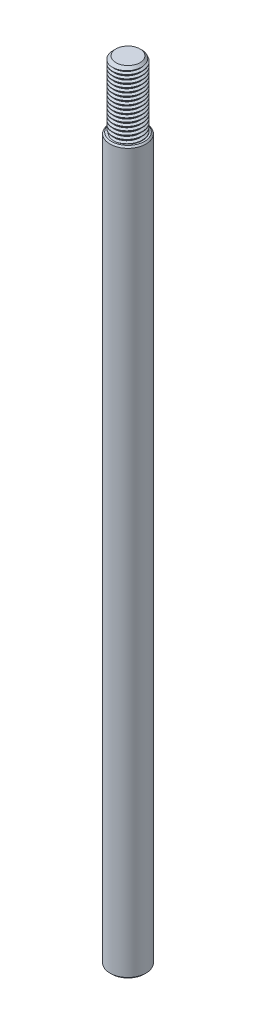
SolidWorks part; units mm, degrees
material "1.8507 (34CrAlMo5-10)"
ref_plane "Front Plane" through (0, 0, 0) normal (0, 0, 1) x (1, 0, 0)
ref_plane "Top Plane" through (0, 0, 0) normal (0, 1, 0) x (1, 0, 0)
ref_plane "Right Plane" through (0, 0, 0) normal (1, 0, 0) x (0, 0, -1)
sketch "Sketch1" plane through (0, 0, 0) normal (0, 1, 0) x (1, 0, 0)
  circle A0 centre (0, 0) radius 6
  dimension "D1" = 12
extrude "Boss-Extrude1" add sketch "Sketch1" along normal blind 262.5
sketch "Sketch4" plane through (0, 262.5, 0) normal (0, 1, 0) x (1, 0, 0)
  circle A0 centre (0, 0) radius 5
  dimension "D1" = 10
extrude "Cut-Extrude1" cut sketch "Sketch4" against normal blind 22 flip side to cut
chamfer "Chamfer2" distance 1 angle 45 1 edges at (0, 262.5, 5)
chamfer "Chamfer3" distance 0.5 angle 45 2 edges at (0, 240.5, 6) (0, 0, 6)
thread "Thread1" pitch 1.25 method cut trim with end face yes profile "Thread Profile2" start angle 0, offset 1, length 0, pitch 1.25, diameter 10
ref_plane "Plane2" through (-5, 262.5, 0) normal (0, 0, 1) x (-1, 0, 0)
sketch "Thread Profile2" plane through (-5, 262.5, 0) normal (0, 0, 1) x (-1, 0, 0)
  line L0 (0, 0) -> (0, 1.25) construction
  line L11 (0, 0) -> (0, 1.0937)
  line L12 (0, 1.0937) -> (-0.6766, 0.7031)
  line L13 (-0.6766, 0.7031) -> (-0.6766, 0.3906)
  line L15 (-0.6766, 0.3906) -> (0, 0)
  line L17 (-0.6766, 0.5469) -> (0, 0.5469) construction
  point P2 (0, 0)
  dimension "Pitch" = 1.25
  dimension "Profile_Angle" = 60
  dimension "Profile_Land" = 0.3125
  dimension "Profile_Height" = 0.6766
